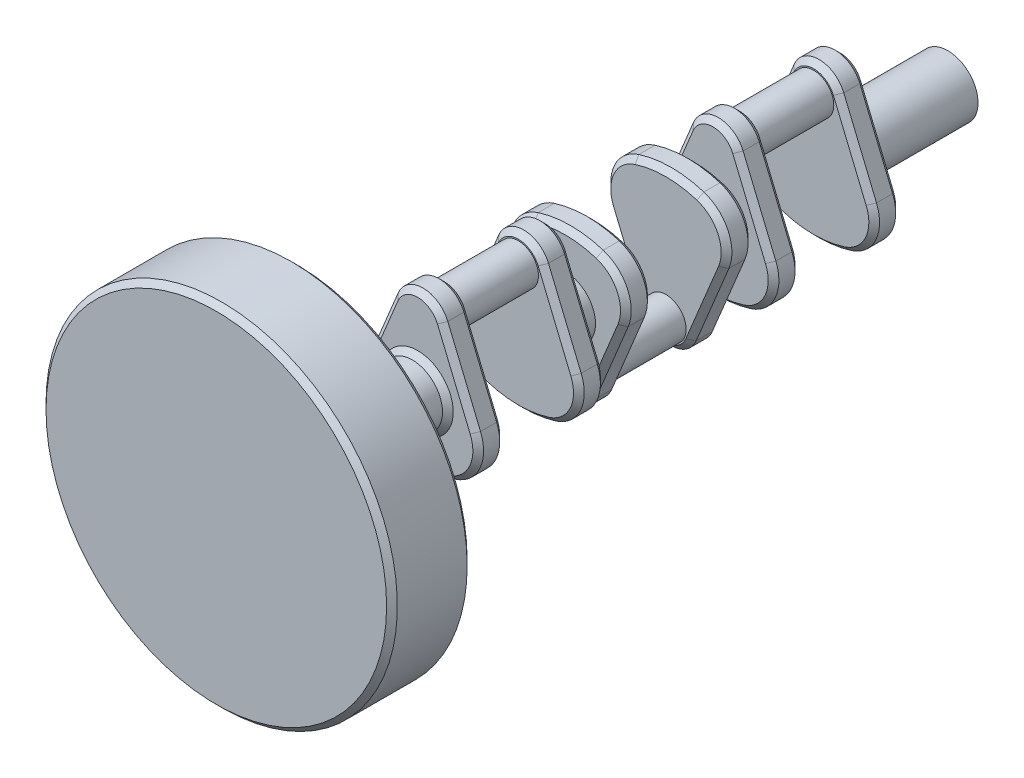
SolidWorks part; units mm, degrees
note: '?' marks a value the reader was unsure of.
material "6061-T6 (SS)"
ref_plane "Front" through (0, 0, 0) normal (0, 0, 1) x (1, 0, 0)
ref_plane "Top" through (0, 0, 0) normal (0, 1, 0) x (1, 0, 0)
ref_plane "Right" through (0, 0, 0) normal (1, 0, 0) x (0, 0, -1)
other "Center of Mass"
sketch "Sketch1" plane through (0, 0, 0) normal (0, 0, 1) x (1, 0, 0)
  circle A1 centre (0, 0) radius 9.525
  dimension "D2" = 19.05
extrude "Boss-Extrude1" add sketch "Sketch1" against normal blind 34.925 contours A1
sketch "Sketch2" plane through (0, 0, -34.925) normal (0, 0, -1) x (-1, 0, 0)
  line L0 (-11.7333, 4.8601) -> (-33.5074, -47.7074)
  line L1 (11.7333, 4.8601) -> (33.5074, -47.7074)
  line L2 (0, 0) -> (0, 30.2986) construction
  arc A0 (11.7333, 4.8601) -> (-11.7333, 4.8601) centre (0, 0) ccw
  arc A1 (-33.5074, -47.7074) -> (33.5074, -47.7074) centre (0, -9.525) ccw
  dimension "D1" = 12.7
  dimension "D2" = 50.8
  dimension "D3" = 45
  dimension "D4" = 9.525
extrude "Boss-Extrude2" add sketch "Sketch2" along normal blind 12.7
fillet "Fillet1" radius 19.05 2 edges at (33.5074, -47.7074, -41.275) (-33.5074, -47.7074, -41.275)
ref_plane "Plane1" through (0, 0, -17.4625) normal (0, 0, 1) x (1, 0, 0)
mirror "Mirror2" about plane through (0, 0, -17.4625) normal (0, 0, 1) of bodies 102
ref_point "Point1"
sketch "Sketch3" plane through (0, 0, -47.625) normal (0, 0, -1) x (-1, 0, 0)
  circle A0 centre (0, -28.4865) radius 14.2875
  point P0 (0, -28.4865)
  dimension "D1" = 28.575
extrude "Boss-Extrude3" add sketch "Sketch3" along normal blind 9.525 separate body
pattern_linear "LPattern1" count 3 spacing 69.85 along (0, 0, -1) of bodies 104
ref_axis "Axis1" through (0, -28.4865, -57.15) along (0, 0, 1)?
move or copy body "Body-Move/Copy1" bodies to move or copy 106 copy no rotation origin (0, -28.4865, 0) rotation axis (0, 0, 1) rotation angle 180
pattern_linear "LPattern2" count 2 spacing 69.85 along (0, 0, -1) of "Boss-Extrude3"
sketch "Sketch4" plane through (0, 0, 12.7) normal (0, 0, 1) x (1, 0, 0)
  circle A0 centre (0, -28.4865) radius 14.2875 construction
  circle A1 centre (0, -28.4865) radius 14.2875
extrude "Boss-Extrude4" add sketch "Sketch4" along normal blind 57.15
sketch "Sketch5" plane through (0, 0, -187.325) normal (0, 0, -1) x (-1, 0, 0)
  line L2 (-11.7333, 4.8601) -> (-27.2069, -32.4965)
  line L3 (27.2069, -32.4965) -> (11.7333, 4.8601)
  line L4 (-11.7333, 4.8601) -> (-27.2069, -32.4965)
  line L5 (27.2069, -32.4965) -> (11.7333, 4.8601)
  circle A0 centre (0, -28.4865) radius 14.2875 construction
  circle A1 centre (0, -28.4865) radius 14.2875
  arc A4 (-27.2069, -32.4965) -> (-15.3712, -57.9437) centre (-9.607, -39.7867) ccw
  arc A5 (-15.3712, -57.9437) -> (15.3712, -57.9437) centre (0, -9.525) ccw
  arc A6 (15.3712, -57.9437) -> (27.2069, -32.4965) centre (9.607, -39.7867) ccw
  arc A7 (11.7333, 4.8601) -> (-11.7333, 4.8601) centre (0, 0) ccw
  arc A8 (-27.2069, -32.4965) -> (-15.3712, -57.9437) centre (-9.607, -39.7867) ccw
  arc A9 (-15.3712, -57.9437) -> (15.3712, -57.9437) centre (0, -9.525) ccw
  arc A10 (15.3712, -57.9437) -> (27.2069, -32.4965) centre (9.607, -39.7867) ccw
  arc A11 (11.7333, 4.8601) -> (-11.7333, 4.8601) centre (0, 0) ccw
  dimension "D1" = 0
extrude "Boss-Extrude5" add sketch "Sketch5" along normal blind 50.8 contours A1
sketch "Sketch6" plane through (0, 0, 69.85) normal (0, 0, 1) x (1, 0, 0)
  circle A0 centre (0, -28.4865) radius 83.1071
extrude "Boss-Extrude6" add sketch "Sketch6" along normal blind 38.1
combine bodies "Combine1" operation type add bodies to combine 105 108 109 111 112
chamfer "Chamfer1" distance 2.54 angle 45 76 edges at (-14.2875, -28.4865, -187.325) (14.2875, -28.4865, 12.7) (-26.8801, -47.8205, -174.625) (-19.4701, -13.8182, -174.625) (0, -60.325, -174.625) (0, 12.7, -174.625) (26.8801, -47.8205, -174.625) (19.4701, -13.8182, -174.625) (-26.8801, -47.8205, -187.325) (-19.4701, -13.8182, -187.325) (0, -60.325, -187.325) (0, 12.7, -187.325) (26.8801, -47.8205, -187.325) (19.4701, -13.8182, -187.325) (-26.8801, -47.8205, -139.7) (-19.4701, -13.8182, -139.7) (0, -60.325, -139.7) (0, 12.7, -139.7) (26.8801, -47.8205, -139.7) (19.4701, -13.8182, -139.7) (-26.8801, -47.8205, -127) (-19.4701, -13.8182, -127) (0, -60.325, -127) (0, 12.7, -127) (26.8801, -47.8205, -127) (19.4701, -13.8182, -127) (-19.4701, -43.1547, -117.475) (-26.8801, -9.1524, -117.475) (0, -69.6729, -117.475) (0, 3.3521, -117.475) (19.4701, -43.1547, -117.475) (26.8801, -9.1524, -117.475) (-19.4701, -43.1547, -104.775) (0, -69.6729, -104.775) (-26.8801, -9.1524, -104.775) (19.4701, -43.1547, -104.775) (0, 3.3521, -104.775) (26.8801, -9.1524, -104.775) (-19.4701, -43.1547, -69.85) (0, -69.6729, -69.85) (-26.8801, -9.1524, -69.85) (19.4701, -43.1547, -69.85) (0, 3.3521, -69.85) (26.8801, -9.1524, -69.85) (-19.4701, -43.1547, -57.15) (-26.8801, -9.1524, -57.15) (0, -69.6729, -57.15) (0, 3.3521, -57.15) (19.4701, -43.1547, -57.15) (26.8801, -9.1524, -57.15) (-19.4701, -13.8182, -47.625) (0, 12.7, -47.625) (-26.8801, -47.8205, -47.625) (19.4701, -13.8182, -47.625) (0, -60.325, -47.625) (26.8801, -47.8205, -47.625) (-19.4701, -13.8182, -34.925) (-26.8801, -47.8205, -34.925) (0, 12.7, -34.925) (0, -60.325, -34.925) (19.4701, -13.8182, -34.925) (26.8801, -47.8205, -34.925) (-19.4701, -13.8182, 0) (-26.8801, -47.8205, 0) (0, 12.7, 0) (0, -60.325, 0) (19.4701, -13.8182, 0) (26.8801, -47.8205, 0) (-19.4701, -13.8182, 12.7) (0, 12.7, 12.7) (-26.8801, -47.8205, 12.7) (19.4701, -13.8182, 12.7) (0, -60.325, 12.7) (26.8801, -47.8205, 12.7) (83.1071, -28.4865, 69.85) (83.1071, -28.4865, 107.95)
ref_plane "Plane2" through (0, 0, 69.85) normal (0, 0, -1) x (-1, 0, 0)
